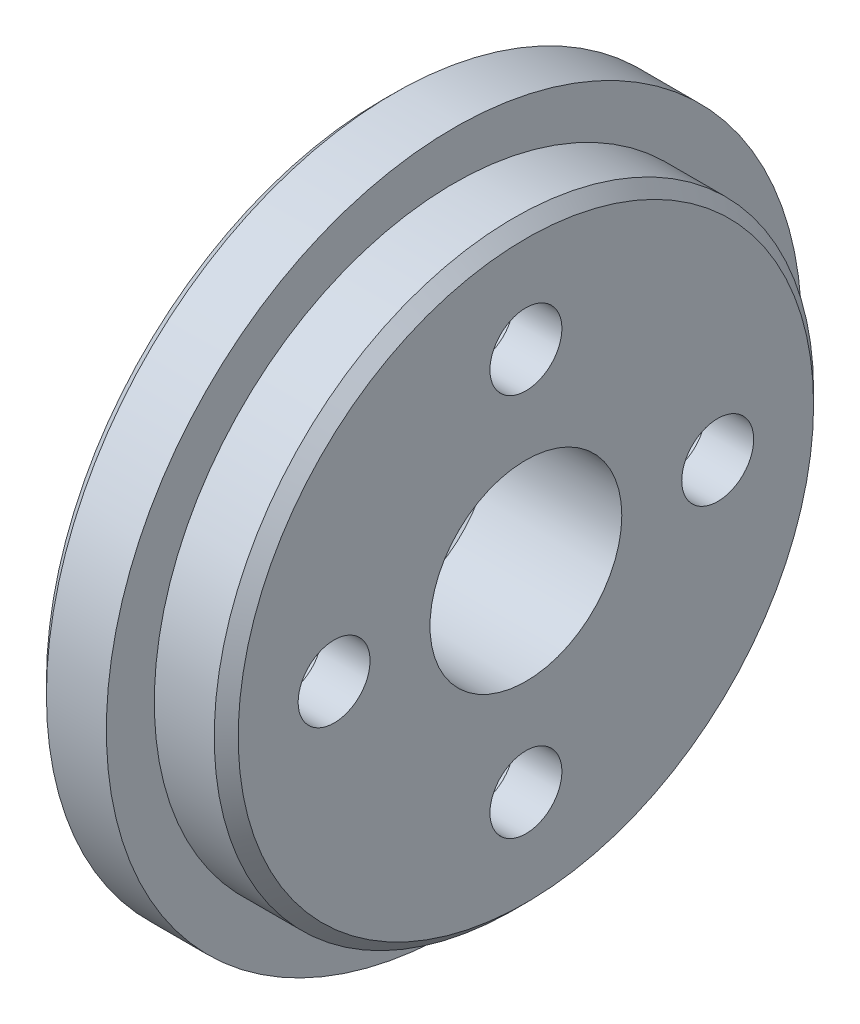
SolidWorks part; units mm, degrees
material "ABS"
ref_plane "Front" through (0, 0, 0) normal (0, 0, 1) x (1, 0, 0)
ref_plane "Top" through (0, 0, 0) normal (0, 1, 0) x (1, 0, 0)
ref_plane "Right" through (0, 0, 0) normal (1, 0, 0) x (0, 0, -1)
sketch "Szkic1" plane through (0, 0, 0) normal (0, 1, 0) x (1, 0, 0)
  line L22 (6, 4) -> (0, 4)
  line L23 (3, 12.5) -> (3, 14.5)
  line L24 (6, 12) -> (6, 4)
  line L25 (3, 14.5) -> (0, 14.5)
  line L26 (6, 12) -> (5.5, 12.5)
  line L27 (5.5, 12.5) -> (3, 12.5)
  line L65 (0, 4) -> (0, 14.5)
  line L117 (7.2113, 0) -> (0, 0) construction
revolve "Obrót2" add sketch "Szkic1" angle 360 about L117
sketch "Szkic2" plane through (0, 0, 0) normal (-1, 0, 0) x (0, 0, 1)
  circle A0 centre (0, 8) radius 3
  circle A1 centre (8, 0) radius 3
  circle A2 centre (0, -8) radius 3
  circle A3 centre (-8, 0) radius 3
  point P12 (0, 0)
  dimension "D1" = 8
  dimension "D2" = 6
  dimension "D3" = 4
extrude "Wytnij-wyciągnięcie1" cut sketch "Szkic2" against normal blind 4
sketch "Szkic3" plane through (0, 0, 0) normal (-1, 0, 0) x (0, 0, 1)
  circle A0 centre (0, 8) radius 1.5
  circle A1 centre (8, 0) radius 1.5
  circle A2 centre (0, -8) radius 1.5
  circle A3 centre (-8, 0) radius 1.5
  point P12 (0, 0)
  dimension "D1" = 3
  dimension "D2" = 4
extrude "Wytnij-wyciągnięcie2" cut sketch "Szkic3" against normal through all
chamfer "Sfazowanie1" distance 0.5 angle 45 7 edges at (0, 0, -14.5) (0, 8, 3) (4, 8, 3) (0, 0, 11) (0, -8, 3) (0, 0, -5) (0, 0, -4)
